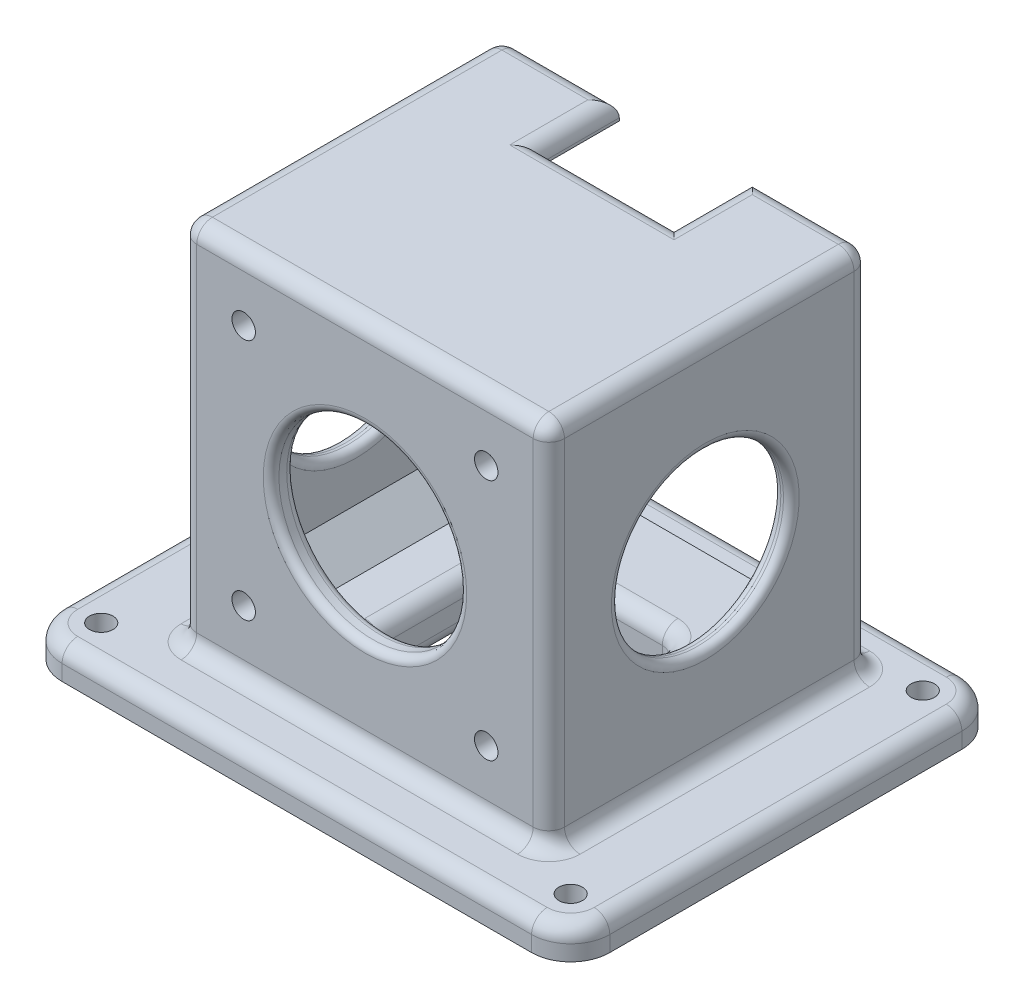
SolidWorks part; units mm, degrees
ref_plane "前视基准面" through (0, 0, 0) normal (0, 0, 1) x (1, 0, 0)
ref_plane "上视基准面" through (0, 0, 0) normal (0, 1, 0) x (1, 0, 0)
ref_plane "右视基准面" through (0, 0, 0) normal (1, 0, 0) x (0, 0, -1)
sketch "草图1" plane through (0, 0, 0) normal (0, 0, 1) x (1, 0, 0)
  line L1 (-21.15, 21.15) -> (21.15, 21.15)
  line L2 (-21.15, 21.15) -> (-21.15, -21.15)
  line L3 (-21.15, -21.15) -> (21.15, -21.15)
  line L4 (21.15, 21.15) -> (21.15, -21.15)
  line L5 (-21.15, 21.15) -> (21.15, -21.15) construction
  line L6 (-21.15, -21.15) -> (21.15, 21.15) construction
  line L7 (-23.5, 23.5) -> (23.5, 23.5)
  line L8 (-23.5, 23.5) -> (-23.5, -23.5)
  line L9 (-23.5, -23.5) -> (23.5, -23.5)
  line L10 (23.5, 23.5) -> (23.5, -23.5)
  line L11 (-23.5, 23.5) -> (23.5, -23.5) construction
  line L12 (-23.5, -23.5) -> (23.5, 23.5) construction
  point P0 (0, 0)
  point P6 (0, 0)
  dimension "D1" = 47
  dimension "D2" = 47
  dimension "D3" = 42.3
  dimension "D4" = 42.3
extrude "凸台-拉伸3" add sketch "草图1" along normal blind 41 contours L8 L7 L10 L9
extrude "切除-拉伸2" cut sketch "草图1<5>" along normal blind 38 contours L2 L1 L4 L3
sketch "草图1<5>" plane through (0, 0, 0) normal (0, 0, 1) x (1, 0, 0) same geometry as "草图1"
chamfer "倒角2" distance 4 angle 45 4 edges at (21.15, -21.15, 19) (-21.15, 21.15, 19) (-21.15, -21.15, 19) (21.15, 21.15, 19)
sketch "草图2" plane through (0, 23.5, 0) normal (0, 1, 0) x (1, 0, 0)
  line L0 (-23.5, 0) -> (23.5, 0) construction
  line L1 (-8.5, 0) -> (8.5, 0)
  line L2 (-8.5, 0) -> (-8.5, -10)
  line L3 (-8.5, -10) -> (8.5, -10)
  line L4 (8.5, 0) -> (8.5, -10)
  line L5 (-23.5, -41) -> (-23.5, 0) construction
  line L6 (23.5, -41) -> (23.5, 0) construction
  dimension "D1" = 10
  dimension "D2" = 17
  dimension "D3" = 15
  dimension "D4" = 15
extrude "切除-拉伸3" cut sketch "草图2" against normal blind 10
sketch "草图3" plane through (0, 0, 41) normal (0, 0, 1) x (1, 0, 0)
  circle A0 centre (0, 0) radius 12
  circle A1 centre (-15.5, 15.5) radius 1.5
  circle A2 centre (15.5, 15.5) radius 1.5
  circle A3 centre (-15.5, -15.5) radius 1.5
  circle A4 centre (15.5, -15.5) radius 1.5
  dimension "D1" = 15.5
  dimension "D2" = 15.5
  dimension "D3" = 31
  dimension "D4" = 15.5
  dimension "D5" = 15.5
  dimension "D6" = 15.5
  dimension "D7" = 15.5
  dimension "D8" = 15.5
extrude "切除-拉伸4" cut sketch "草图3" against normal blind 10
sketch "草图4" plane through (0, -23.5, 0) normal (0, -1, 0) x (1, 0, 0)
  line L0 (-23.5, 41) -> (23.5, 41) construction
  line L1 (-35.7084, 49) -> (34.2916, 49)
  line L2 (-35.7084, 49) -> (-35.7084, -6)
  line L3 (-35.7084, -6) -> (34.2916, -6)
  line L4 (34.2916, 49) -> (34.2916, -6)
  line L5 (-35.7084, 49) -> (34.2916, -6) construction
  line L6 (-35.7084, -6) -> (34.2916, 49) construction
  line L7 (-23.5, 0) -> (23.5, 0) construction
  circle A0 centre (-30.7084, 44) radius 1.5
  circle A1 centre (29.2916, 44) radius 1.5
  circle A2 centre (29.2916, -1) radius 1.5
  circle A3 centre (-30.7084, -1) radius 1.5
  point P0 (-0.7084, 21.5)
  dimension "D6" = 5
  dimension "D1" = 70
  dimension "D2" = 21.5
  dimension "D3" = 55
  dimension "D4" = 8
  dimension "D5" = 6
  dimension "D7" = 5
  dimension "D8" = 5
  dimension "D9" = 5
  dimension "D10" = 5
  dimension "D11" = 5
  dimension "D12" = 5
  dimension "D13" = 5
extrude "凸台-拉伸4" add sketch "草图4" along normal blind 4
fillet "圆角4" radius 5 4 edges at (34.2916, -25.5, 49) (-35.7084, -25.5, 49) (-35.7084, -25.5, -6) (34.2916, -25.5, -6)
fillet "圆角5" radius 2 24 edges at (0, -23.5, 41) (0, -23.5, 0) (0, 23.5, 10) (8.5, 23.5, 5) (16, 23.5, 0) (0, 23.5, 41) (-16, 23.5, 0) (-8.5, 23.5, 5) (-34.244, -23.5, 47.5355) (-35.7084, -23.5, 21.5) (-34.244, -23.5, -4.5355) (-0.7084, -23.5, -6) (32.8271, -23.5, -4.5355) (34.2916, -23.5, 21.5) (32.8271, -23.5, 47.5355) (-0.7084, -23.5, 49) (-23.5, 23.5, 20.5) (-23.5, 0, 41) (-23.5, -23.5, 20.5) (-23.5, 0, 0) (23.5, -23.5, 20.5) (23.5, 0, 41) (23.5, 23.5, 20.5) (23.5, 0, 0)
sketch "草图5" plane through (-23.5, 0, 0) normal (-1, 0, 0) x (0, 0, 1)
  line L0 (39, 21.5) -> (2, 21.5) construction
  line L1 (0, -21.5) -> (0, 21.5) construction
  circle A0 centre (21, 0) radius 11
  point P4 (0, 0)
  point P6 (20.0052, -2.9291)
  dimension "D1" = 21.5
  dimension "D2" = 21
extrude "切除-拉伸5" cut sketch "草图5" against normal blind 47
sketch "草图7" plane through (0, -21.15, 0) normal (0, 1, 0) x (1, 0, 0)
  line L0 (-17.15, 0) -> (17.15, 0) construction
  line L1 (-10, -11) -> (10, -11)
  line L2 (-10, -11) -> (-10, -31)
  line L3 (-10, -31) -> (10, -31)
  line L4 (10, -11) -> (10, -31)
  line L5 (-10, -11) -> (10, -31) construction
  line L6 (-10, -31) -> (10, -11) construction
  point P0 (0, -21)
  dimension "D1" = 21
  dimension "D2" = 20
  dimension "D3" = 20
extrude "切除-拉伸6" cut sketch "草图7" against normal blind 47
fillet "圆角6" radius 2 12 edges at (10, -27.5, 21) (10, -21.15, 21) (-10, -21.15, 21) (-10, -27.5, 21) (-10, -24.325, 11) (0, -21.15, 11) (10, -24.325, 11) (0, -27.5, 11) (10, -24.325, 31) (0, -21.15, 31) (-10, -24.325, 31) (0, -27.5, 31)
fillet "圆角7" radius 1 4 edges at (21.15, 11, 21) (23.5, -11, 21) (-23.5, -11, 21) (-21.15, 11, 21)
fillet "圆角8" radius 1 2 edges at (12, 0, 41) (-12, 0, 38)
